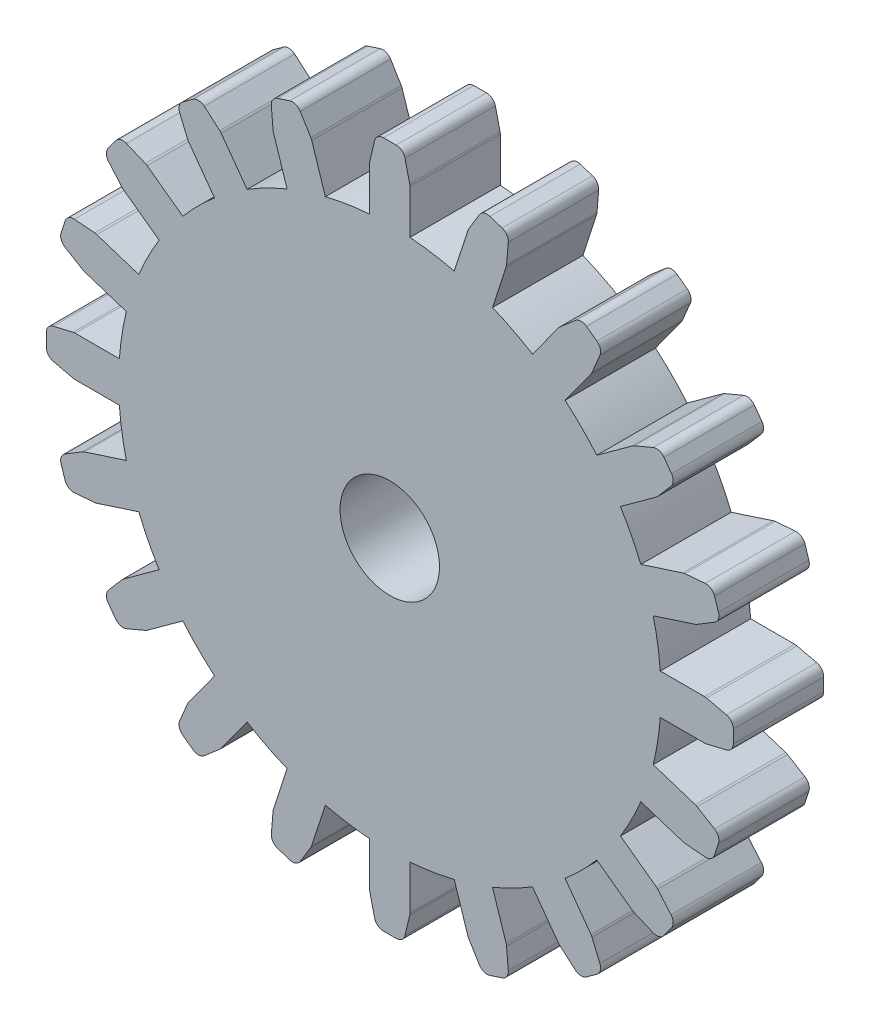
SolidWorks part; units mm, degrees
ref_plane "Front Plane" through (0, 0, 0) normal (0, 0, 1) x (1, 0, 0)
ref_plane "Top Plane" through (0, 0, 0) normal (0, 1, 0) x (1, 0, 0)
ref_plane "Right Plane" through (0, 0, 0) normal (1, 0, 0) x (0, 0, -1)
sketch "Sketch1" plane through (0, 0, 0) normal (0, 0, 1) x (1, 0, 0)
  line L0 (0, 0) -> (0, 46.6791) construction
  line L1 (-0.75, 19) -> (0.75, 19)
  line L3 (-1.1127, 14.9587) -> (-1.1127, 17.4587)
  line L5 (1.1127, 14.9587) -> (1.1127, 17.4587)
  line L6 (3.5643, 14.5704) -> (4.3368, 16.948)
  line L7 (5.158, 18.3018) -> (4.3368, 16.948)
  line L8 (-0.75, 19) -> (-1.1127, 17.4587)
  line L9 (0.75, 19) -> (1.1127, 17.4587)
  line L10 (5.158, 18.3018) -> (6.5846, 17.8383)
  line L11 (6.5846, 17.8383) -> (6.4532, 16.2604)
  line L12 (5.6807, 13.8827) -> (6.4532, 16.2604)
  line L13 (7.8923, 12.7558) -> (9.3618, 14.7784)
  line L14 (10.5612, 15.8122) -> (9.3618, 14.7784)
  line L15 (10.5612, 15.8122) -> (11.7747, 14.9305)
  line L16 (11.7747, 14.9305) -> (11.1621, 13.4704)
  line L17 (9.6927, 11.4478) -> (11.1621, 13.4704)
  line L18 (11.4478, 9.6927) -> (13.4704, 11.1621)
  line L19 (14.9305, 11.7747) -> (13.4704, 11.1621)
  line L20 (14.9305, 11.7747) -> (15.8122, 10.5612)
  line L21 (15.8122, 10.5612) -> (14.7784, 9.3618)
  line L22 (12.7558, 7.8923) -> (14.7784, 9.3618)
  line L23 (13.8827, 5.6807) -> (16.2604, 6.4532)
  line L24 (17.8383, 6.5846) -> (16.2604, 6.4532)
  line L25 (17.8383, 6.5846) -> (18.3018, 5.158)
  line L26 (18.3018, 5.158) -> (16.948, 4.3368)
  line L27 (14.5704, 3.5643) -> (16.948, 4.3368)
  line L28 (14.9587, 1.1127) -> (17.4587, 1.1127)
  line L29 (19, 0.75) -> (17.4587, 1.1127)
  line L30 (19, 0.75) -> (19, -0.75)
  line L31 (19, -0.75) -> (17.4587, -1.1127)
  line L32 (14.9587, -1.1127) -> (17.4587, -1.1127)
  line L33 (14.5704, -3.5643) -> (16.948, -4.3368)
  line L34 (18.3018, -5.158) -> (16.948, -4.3368)
  line L35 (18.3018, -5.158) -> (17.8383, -6.5846)
  line L36 (17.8383, -6.5846) -> (16.2604, -6.4532)
  line L37 (13.8827, -5.6807) -> (16.2604, -6.4532)
  line L38 (12.7558, -7.8923) -> (14.7784, -9.3618)
  line L39 (15.8122, -10.5612) -> (14.7784, -9.3618)
  line L40 (15.8122, -10.5612) -> (14.9305, -11.7747)
  line L41 (14.9305, -11.7747) -> (13.4704, -11.1621)
  line L42 (11.4478, -9.6927) -> (13.4704, -11.1621)
  line L43 (9.6927, -11.4478) -> (11.1621, -13.4704)
  line L44 (11.7747, -14.9305) -> (11.1621, -13.4704)
  line L45 (11.7747, -14.9305) -> (10.5612, -15.8122)
  line L46 (10.5612, -15.8122) -> (9.3618, -14.7784)
  line L47 (7.8923, -12.7558) -> (9.3618, -14.7784)
  line L48 (5.6807, -13.8827) -> (6.4532, -16.2604)
  line L49 (6.5846, -17.8383) -> (6.4532, -16.2604)
  line L50 (6.5846, -17.8383) -> (5.158, -18.3018)
  line L51 (5.158, -18.3018) -> (4.3368, -16.948)
  line L52 (3.5643, -14.5704) -> (4.3368, -16.948)
  line L53 (1.1127, -14.9587) -> (1.1127, -17.4587)
  line L54 (0.75, -19) -> (1.1127, -17.4587)
  line L55 (0.75, -19) -> (-0.75, -19)
  line L56 (-0.75, -19) -> (-1.1127, -17.4587)
  line L57 (-1.1127, -14.9587) -> (-1.1127, -17.4587)
  line L58 (-3.5643, -14.5704) -> (-4.3368, -16.948)
  line L59 (-5.158, -18.3018) -> (-4.3368, -16.948)
  line L60 (-5.158, -18.3018) -> (-6.5846, -17.8383)
  line L61 (-6.5846, -17.8383) -> (-6.4532, -16.2604)
  line L62 (-5.6807, -13.8827) -> (-6.4532, -16.2604)
  line L63 (-7.8923, -12.7558) -> (-9.3618, -14.7784)
  line L64 (-10.5612, -15.8122) -> (-9.3618, -14.7784)
  line L65 (-10.5612, -15.8122) -> (-11.7747, -14.9305)
  line L66 (-11.7747, -14.9305) -> (-11.1621, -13.4704)
  line L67 (-9.6927, -11.4478) -> (-11.1621, -13.4704)
  line L68 (-11.4478, -9.6927) -> (-13.4704, -11.1621)
  line L69 (-14.9305, -11.7747) -> (-13.4704, -11.1621)
  line L70 (-14.9305, -11.7747) -> (-15.8122, -10.5612)
  line L71 (-15.8122, -10.5612) -> (-14.7784, -9.3618)
  line L72 (-12.7558, -7.8923) -> (-14.7784, -9.3618)
  line L73 (-13.8827, -5.6807) -> (-16.2604, -6.4532)
  line L74 (-17.8383, -6.5846) -> (-16.2604, -6.4532)
  line L75 (-17.8383, -6.5846) -> (-18.3018, -5.158)
  line L76 (-18.3018, -5.158) -> (-16.948, -4.3368)
  line L77 (-14.5704, -3.5643) -> (-16.948, -4.3368)
  line L78 (-14.9587, -1.1127) -> (-17.4587, -1.1127)
  line L79 (-19, -0.75) -> (-17.4587, -1.1127)
  line L80 (-19, -0.75) -> (-19, 0.75)
  line L81 (-19, 0.75) -> (-17.4587, 1.1127)
  line L82 (-14.9587, 1.1127) -> (-17.4587, 1.1127)
  line L83 (-14.5704, 3.5643) -> (-16.948, 4.3368)
  line L84 (-18.3018, 5.158) -> (-16.948, 4.3368)
  line L85 (-18.3018, 5.158) -> (-17.8383, 6.5846)
  line L86 (-17.8383, 6.5846) -> (-16.2604, 6.4532)
  line L87 (-13.8827, 5.6807) -> (-16.2604, 6.4532)
  line L88 (-12.7558, 7.8923) -> (-14.7784, 9.3618)
  line L89 (-15.8122, 10.5612) -> (-14.7784, 9.3618)
  line L90 (-15.8122, 10.5612) -> (-14.9305, 11.7747)
  line L91 (-14.9305, 11.7747) -> (-13.4704, 11.1621)
  line L92 (-11.4478, 9.6927) -> (-13.4704, 11.1621)
  line L93 (-9.6927, 11.4478) -> (-11.1621, 13.4704)
  line L94 (-11.7747, 14.9305) -> (-11.1621, 13.4704)
  line L95 (-11.7747, 14.9305) -> (-10.5612, 15.8122)
  line L96 (-10.5612, 15.8122) -> (-9.3618, 14.7784)
  line L97 (-7.8923, 12.7558) -> (-9.3618, 14.7784)
  line L98 (-5.6807, 13.8827) -> (-6.4532, 16.2604)
  line L99 (-6.5846, 17.8383) -> (-6.4532, 16.2604)
  line L100 (-6.5846, 17.8383) -> (-5.158, 18.3018)
  line L101 (-5.158, 18.3018) -> (-4.3368, 16.948)
  line L102 (-3.5643, 14.5704) -> (-4.3368, 16.948)
  circle A0 centre (0, 0) radius 2.75
  arc A1 (-1.1127, 14.9587) -> (-3.5643, 14.5704) centre (0, 0) ccw
  arc A2 (3.5643, 14.5704) -> (1.1127, 14.9587) centre (0, 0) ccw
  arc A3 (7.8923, 12.7558) -> (5.6807, 13.8827) centre (0, 0) ccw
  arc A4 (11.4478, 9.6927) -> (9.6927, 11.4478) centre (0, 0) ccw
  arc A5 (13.8827, 5.6807) -> (12.7558, 7.8923) centre (0, 0) ccw
  arc A6 (14.9587, 1.1127) -> (14.5704, 3.5643) centre (0, 0) ccw
  arc A7 (14.5704, -3.5643) -> (14.9587, -1.1127) centre (0, 0) ccw
  arc A8 (12.7558, -7.8923) -> (13.8827, -5.6807) centre (0, 0) ccw
  arc A9 (9.6927, -11.4478) -> (11.4478, -9.6927) centre (0, 0) ccw
  arc A10 (5.6807, -13.8827) -> (7.8923, -12.7558) centre (0, 0) ccw
  arc A11 (1.1127, -14.9587) -> (3.5643, -14.5704) centre (0, 0) ccw
  arc A12 (-3.5643, -14.5704) -> (-1.1127, -14.9587) centre (0, 0) ccw
  arc A13 (-7.8923, -12.7558) -> (-5.6807, -13.8827) centre (0, 0) ccw
  arc A14 (-11.4478, -9.6927) -> (-9.6927, -11.4478) centre (0, 0) ccw
  arc A15 (-13.8827, -5.6807) -> (-12.7558, -7.8923) centre (0, 0) ccw
  arc A16 (-14.5704, 3.5643) -> (-14.9587, 1.1127) centre (0, 0) ccw
  arc A17 (-14.9587, -1.1127) -> (-14.5704, -3.5643) centre (0, 0) ccw
  arc A18 (-12.7558, 7.8923) -> (-13.8827, 5.6807) centre (0, 0) ccw
  arc A19 (-9.6927, 11.4478) -> (-11.4478, 9.6927) centre (0, 0) ccw
  arc A20 (-5.6807, 13.8827) -> (-7.8923, 12.7558) centre (0, 0) ccw
  point P4 (0, 15)
  point P12 (0, 19)
  point P128 (0, 0)
  dimension "D1" = 15
  dimension "D2" = 5.5
  dimension "D3" = 2.5
  dimension "D4" = 2.5
  dimension "D5" = 1.5
  dimension "D7" = 4
  dimension "D8" = 2.5
  dimension "D6" = 20
extrude "Boss-Extrude1" add sketch "Sketch1" along normal blind 5
fillet "Fillet3" radius 0.5 1 edges at (0.75, 19, 2.5)
fillet "Fillet4" radius 0.5 1 edges at (-0.75, 19, 2.5)
fillet "Fillet5" radius 0.5 1 edges at (1.1127, 17.4587, 2.5)
fillet "Fillet6" radius 0.5 1 edges at (-1.1127, 17.4587, 2.5)
fillet "Fillet7" radius 0.5 1 edges at (6.5846, 17.8383, 2.5)
fillet "Fillet8" radius 0.5 1 edges at (5.158, 18.3018, 2.5)
fillet "Fillet9" radius 0.5 1 edges at (10.5612, 15.8122, 2.5)
fillet "Fillet10" radius 0.5 1 edges at (11.7747, 14.9305, 2.5)
fillet "Fillet11" radius 0.5 1 edges at (15.8122, 10.5612, 2.5)
fillet "Fillet12" radius 0.5 1 edges at (14.9305, 11.7747, 2.5)
fillet "Fillet13" radius 0.5 1 edges at (17.8383, 6.5846, 2.5)
fillet "Fillet14" radius 0.5 1 edges at (18.3018, 5.158, 2.5)
fillet "Fillet15" radius 0.5 1 edges at (19, 0.75, 2.5)
fillet "Fillet16" radius 0.5 1 edges at (19, -0.75, 2.5)
fillet "Fillet17" radius 0.5 1 edges at (18.3018, -5.158, 2.5)
fillet "Fillet18" radius 0.5 1 edges at (17.8383, -6.5846, 2.5)
fillet "Fillet19" radius 0.5 1 edges at (15.8122, -10.5612, 2.5)
fillet "Fillet20" radius 0.5 1 edges at (14.9305, -11.7747, 2.5)
fillet "Fillet21" radius 0.5 1 edges at (11.7747, -14.9305, 2.5)
fillet "Fillet22" radius 0.5 1 edges at (10.5612, -15.8122, 2.5)
fillet "Fillet23" radius 0.5 1 edges at (6.5846, -17.8383, 2.5)
fillet "Fillet24" radius 0.5 1 edges at (5.158, -18.3018, 2.5)
fillet "Fillet25" radius 0.5 1 edges at (0.75, -19, 2.5)
fillet "Fillet26" radius 0.5 1 edges at (-0.75, -19, 2.5)
fillet "Fillet27" radius 0.5 1 edges at (-5.158, -18.3018, 2.5)
fillet "Fillet28" radius 0.5 1 edges at (-6.5846, -17.8383, 2.5)
fillet "Fillet29" radius 0.5 1 edges at (-10.5612, -15.8122, 2.5)
fillet "Fillet30" radius 0.5 1 edges at (-11.7747, -14.9305, 2.5)
fillet "Fillet31" radius 0.5 1 edges at (-14.9305, -11.7747, 2.5)
fillet "Fillet32" radius 0.5 1 edges at (-15.8122, -10.5612, 2.5)
fillet "Fillet33" radius 0.5 1 edges at (-17.8383, -6.5846, 2.5)
fillet "Fillet34" radius 0.5 1 edges at (-18.3018, -5.158, 2.5)
fillet "Fillet35" radius 0.5 1 edges at (-19, -0.75, 2.5)
fillet "Fillet36" radius 0.5 1 edges at (-19, 0.75, 2.5)
fillet "Fillet37" radius 0.5 1 edges at (-18.3018, 5.158, 2.5)
fillet "Fillet38" radius 0.5 1 edges at (-17.8383, 6.5846, 2.5)
fillet "Fillet39" radius 0.5 1 edges at (-15.8122, 10.5612, 2.5)
fillet "Fillet40" radius 0.5 1 edges at (-14.9305, 11.7747, 2.5)
fillet "Fillet41" radius 0.5 1 edges at (-11.7747, 14.9305, 2.5)
fillet "Fillet42" radius 0.5 1 edges at (-10.5612, 15.8122, 2.5)
fillet "Fillet43" radius 0.5 1 edges at (-6.5846, 17.8383, 2.5)
fillet "Fillet44" radius 0.5 1 edges at (-5.158, 18.3018, 2.5)
fillet "Fillet45" radius 0.5 1 edges at (4.3368, 16.948, 2.5)
fillet "Fillet46" radius 0.5 1 edges at (6.4532, 16.2604, 2.5)
fillet "Fillet47" radius 0.5 1 edges at (9.3618, 14.7784, 2.5)
fillet "Fillet48" radius 0.5 1 edges at (11.1621, 13.4704, 2.5)
fillet "Fillet49" radius 0.5 1 edges at (13.4704, 11.1621, 2.5)
fillet "Fillet50" radius 0.5 1 edges at (14.7784, 9.3618, 2.5)
fillet "Fillet51" radius 0.5 1 edges at (16.2604, 6.4532, 2.5)
fillet "Fillet52" radius 0.5 1 edges at (16.948, 4.3368, 2.5)
fillet "Fillet53" radius 0.5 1 edges at (17.4587, 1.1127, 2.5)
fillet "Fillet54" radius 0.5 1 edges at (17.4587, -1.1127, 2.5)
fillet "Fillet55" radius 0.5 1 edges at (16.948, -4.3368, 2.5)
fillet "Fillet56" radius 0.5 1 edges at (16.2604, -6.4532, 2.5)
fillet "Fillet57" radius 0.5 1 edges at (14.7784, -9.3618, 2.5)
fillet "Fillet58" radius 0.5 1 edges at (13.4704, -11.1621, 2.5)
fillet "Fillet59" radius 0.5 1 edges at (11.1621, -13.4704, 2.5)
fillet "Fillet60" radius 0.5 1 edges at (9.3618, -14.7784, 2.5)
fillet "Fillet61" radius 0.5 1 edges at (6.4532, -16.2604, 2.5)
fillet "Fillet62" radius 0.5 1 edges at (4.3368, -16.948, 2.5)
fillet "Fillet63" radius 0.5 1 edges at (-1.1127, -17.4587, 2.5)
fillet "Fillet64" radius 0.5 1 edges at (1.1127, -17.4587, 2.5)
fillet "Fillet65" radius 0.5 1 edges at (-4.3368, -16.948, 2.5)
fillet "Fillet66" radius 0.5 1 edges at (-6.4532, -16.2604, 2.5)
fillet "Fillet67" radius 0.5 1 edges at (-9.3618, -14.7784, 2.5)
fillet "Fillet70" radius 0.5 1 edges at (-13.4704, -11.1621, 2.5)
fillet "Fillet71" radius 0.5 1 edges at (-14.7784, -9.3618, 2.5)
fillet "Fillet72" radius 0.5 1 edges at (-16.2604, -6.4532, 2.5)
fillet "Fillet73" radius 0.5 1 edges at (-16.948, -4.3368, 2.5)
fillet "Fillet74" radius 0.5 1 edges at (-17.4587, 1.1127, 2.5)
fillet "Fillet75" radius 0.5 1 edges at (-17.4587, -1.1127, 2.5)
fillet "Fillet76" radius 0.5 1 edges at (-16.948, 4.3368, 2.5)
fillet "Fillet77" radius 0.5 1 edges at (-16.2604, 6.4532, 2.5)
fillet "Fillet78" radius 0.5 1 edges at (-14.7784, 9.3618, 2.5)
fillet "Fillet79" radius 0.5 1 edges at (-13.4704, 11.1621, 2.5)
fillet "Fillet80" radius 0.5 1 edges at (-11.1621, 13.4704, 2.5)
fillet "Fillet81" radius 0.5 1 edges at (-9.3618, 14.7784, 2.5)
fillet "Fillet82" radius 0.5 1 edges at (-6.4532, 16.2604, 2.5)
fillet "Fillet83" radius 0.5 1 edges at (-4.3368, 16.948, 2.5)
